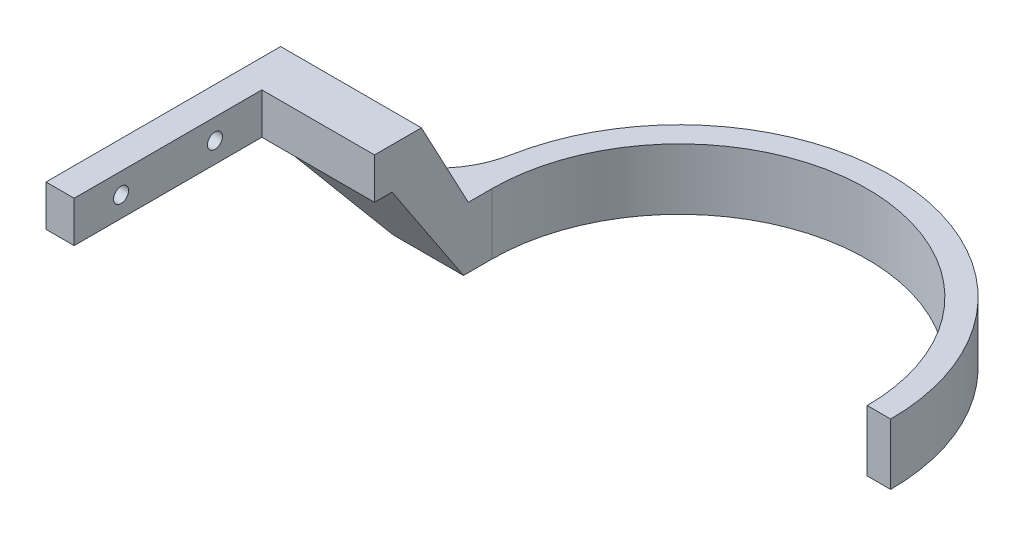
SolidWorks part; units mm, degrees
material "ABS"
ref_plane "前基準面" through (0, 0, 0) normal (0, 0, 1) x (1, 0, 0)
ref_plane "上基準面" through (0, 0, 0) normal (0, 1, 0) x (1, 0, 0)
ref_plane "右基準面" through (0, 0, 0) normal (1, 0, 0) x (0, 0, -1)
sketch "草圖1" plane through (0, 0, 0) normal (0, 1, 0) x (1, 0, 0)
  line L2 (-45, 0) -> (-40, 0)
  line L3 (40, 0) -> (45, 0)
  arc A0 (-40, 0) -> (40, 0) centre (0, 0) cw
  arc A2 (-45, 0) -> (45, 0) centre (0, 0) cw
  dimension "D1" = 40
  dimension "D2" = 5
extrude "填料-伸長1" add sketch "草圖1" along normal blind 13
ref_plane "平面1" through (-40, 0, 0) normal (1, 0, 0) x (0, 0, -1)
sketch "草圖2" plane through (0, 0, 0) normal (0, 0, 1) x (1, 0, 0)
  line L0 (-45, 0) -> (-40, 0) construction
  line L1 (-40, 13) -> (-70, 13)
  line L2 (-40, 13) -> (-40, 0)
  line L3 (-40, 0) -> (-70, 0)
  line L4 (-70, 13) -> (-70, 0)
  dimension "D1" = 30
extrude "填料-伸長2" add sketch "草圖2" along normal blind 5
sketch "草圖3" plane through (-40, 0, 0) normal (1, 0, 0) x (0, 0, -1)
  line L0 (-5, 0) -> (-5, 13)
  line L1 (-5, 0) -> (-15, 23)
  line L2 (-5, 13) -> (-15, 31.75)
  line L3 (-15, 23) -> (-15, 31.75)
  dimension "D1" = 8.75
  dimension "D2" = 10
  dimension "D3" = 10
extrude "填料-伸長3" add sketch "草圖3" against normal up to surface (30 mm away) up to face at (-70, 6.5, 2.5)
sketch "草圖4" plane through (0, 0, 15) normal (0, 0, 1) x (1, 0, 0)
  line L4 (-70, 31.75) -> (-70, 23)
  line L5 (-70, 23) -> (-40, 23)
  line L6 (-40, 23) -> (-40, 31.75)
  line L7 (-40, 31.75) -> (-70, 31.75)
  line L8 (-70, 31.75) -> (-70, 23)
  line L9 (-70, 23) -> (-40, 23)
  line L10 (-40, 23) -> (-40, 31.75)
  line L11 (-40, 31.75) -> (-70, 31.75)
  dimension "D1" = 0
extrude "填料-伸長4" add sketch "草圖4" along normal blind 10
sketch "草圖8" plane through (0, 13, 0) normal (0, 1, 0) x (1, 0, 0)
  line L0 (-45, 0) -> (-70, -15)
  line L1 (-70, -15) -> (-70, 0)
  line L2 (-70, 0) -> (-45, 0)
  line L3 (-70, -5) -> (-70, 0) construction
extrude "除料-伸長3" cut sketch "草圖8" against normal through all both and the other way through all
sketch "草圖9" plane through (-70, 0, 0) normal (-1, 0, 0) x (0, 0, 1)
  line L0 (25, 23) -> (15, 23) construction
  line L1 (25, 31.75) -> (65, 31.75)
  line L2 (25, 31.75) -> (25, 23)
  line L3 (25, 23) -> (65, 23)
  line L4 (65, 31.75) -> (65, 23)
  dimension "D1" = 40
extrude "填料-伸長5" add sketch "草圖9" against normal blind 6
sketch "草圖10" plane through (-64, 0, 0) normal (1, 0, 0) x (0, 0, -1)
  line L0 (-65, 27.375) -> (-25, 27.375) construction
  line L1 (-65, 23) -> (-65, 31.75) construction
  line L2 (-25, 31.75) -> (-25, 23) construction
  circle A0 centre (-35, 27.375) radius 1.6
  dimension "D1" = 10
  dimension "D2" = 3.2
extrude "除料-伸長4" cut sketch "草圖10" against normal through all
pattern_linear "直線複製排列1" count 2 spacing 20 along (0, 0, 1) of "除料-伸長4"
chamfer "導角3" distance 30 angle 10 1 edges at (-55, 23, 15) first distance on face at (-50.8333, 11.5, 10)
fillet "圓角1" radius 20 1 edges at (-45, 6.5, 0)
